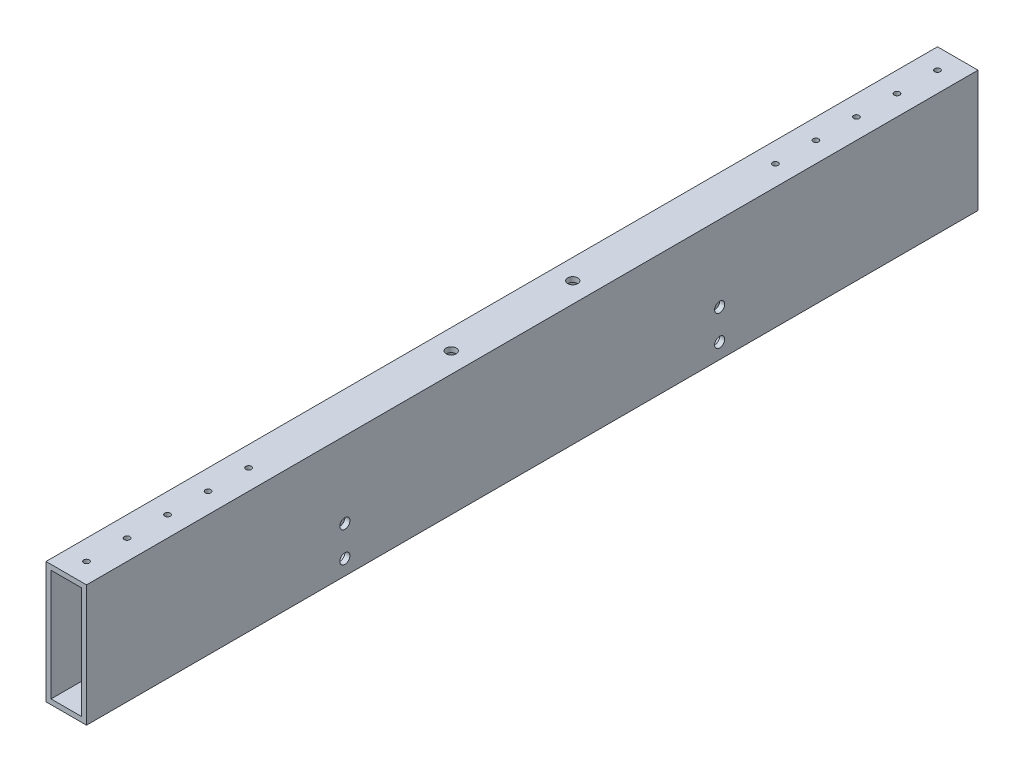
SolidWorks part; units mm, degrees
material "6061-T6 (SS)"
ref_plane "Front Plane" through (0, 0, 0) normal (0, 0, 1) x (1, 0, 0)
ref_plane "Top Plane" through (0, 0, 0) normal (0, 1, 0) x (1, 0, 0)
ref_plane "Right Plane" through (0, 0, 0) normal (1, 0, 0) x (0, 0, -1)
sketch "Sketch1" plane through (0, 0, 0) normal (0, 0, 1) x (1, 0, 0)
  line L0 (9.525, 34.925) -> (-9.525, 34.925)
  line L1 (12.7, 38.1) -> (-12.7, 38.1)
  line L2 (12.7, 38.1) -> (12.7, -38.1)
  line L3 (12.7, -38.1) -> (-12.7, -38.1)
  line L4 (-12.7, 38.1) -> (-12.7, -38.1)
  line L5 (12.7, 38.1) -> (-12.7, -38.1) construction
  line L6 (12.7, -38.1) -> (-12.7, 38.1) construction
  line L7 (-9.525, 34.925) -> (-9.525, -34.925)
  line L8 (9.525, -34.925) -> (-9.525, -34.925)
  line L9 (9.525, 34.925) -> (9.525, -34.925)
  point P0 (0, 0)
  dimension "D1" = 76.2
  dimension "D2" = 25.4
  dimension "D3" = 3.175
extrude "Boss-Extrude1" add sketch "Sketch1" along normal mid plane 558.8
sketch "Sketch2" plane through (0, 38.1, 0) normal (0, 1, 0) x (1, 0, 0)
  line L1 (12.7, 279.4) -> (-12.7, 279.4) construction
  circle A0 centre (0, 266.7) radius 1.7272
  circle A1 centre (0, 241.3) radius 1.7272
  circle A2 centre (0, 215.9) radius 1.7272
  circle A3 centre (0, 190.5) radius 1.7272
  circle A8 centre (0, 165.1) radius 1.7272
  dimension "D1" = 3.4544
  dimension "D2" = 12.7
  dimension "D3" = 5
sketch "Sketch3" plane through (0, -38.1, 0) normal (0, -1, 0) x (1, 0, 0)
  line L2 (9.525, 279.4) -> (-9.525, 279.4) construction
  circle A0 centre (0, 254) radius 1.7272
  circle A1 centre (0, 203.2) radius 1.7272
  circle A2 centre (0, 152.4) radius 1.7272
  circle A3 centre (0, 101.6) radius 1.7272
  circle A4 centre (0, 50.8) radius 1.7272
  circle A5 centre (0, 0) radius 1.7272
  circle A6 centre (0, -50.8) radius 1.7272
  circle A7 centre (0, -101.6) radius 1.7272
  circle A8 centre (0, -152.4) radius 1.7272
  circle A9 centre (0, -203.2) radius 1.7272
  circle A10 centre (0, -254) radius 1.7272
  point P6 (0, 279.4)
  dimension "D1" = 3.4544
  dimension "D2" = 25.4
  dimension "D4" = 50.8
  dimension "D3" = 11
extrude "Cut-Extrude2" cut sketch "Sketch3" against normal blind 6.35
hole_wizard "1/4 (0.25) Diameter Hole1" positions "Sketch9" profile "Sketch8" hole size "1/4" standard "ANSI Inch"
sketch "Sketch9" plane through (-12.7, 0, 0) normal (-1, 0, 0) x (0, 0, 1)
  line L0 (-117.475, -28.575) -> (117.475, -28.575) construction
  line L2 (279.4, -38.1) -> (-279.4, -38.1) construction
  line L4 (-127, 0) -> (127, 0) construction
  point P10 (-117.475, -28.575)
  point P11 (117.475, -28.575)
  point P25 (-117.475, -9.525)
  point P27 (117.475, -9.525)
  point P34 (0, -28.575)
  dimension "D1" = 234.95
  dimension "D2" = 9.525
  dimension "D3" = 254
  dimension "D4" = 19.05
  dimension "D5" = 19.05
sketch "Sketch8" plane through (-12.7, -28.575, -117.475) normal (0, 1, 0) x (0, 0, 1)
  line L0 (0, 0) -> (0, 27.3077)
  line L1 (0, 27.3077) -> (3.175, 25.4)
  line L2 (3.175, 25.4) -> (3.175, 0)
  line L5 (3.175, 0) -> (0, 0)
  line L10 (0, 27.3077) -> (-3.175, 25.4) construction
  line L11 (0, -6.35) -> (0, 107.95) construction
  dimension "Hole Dia." = 6.35
  dimension "Hole Depth" = 25.4
  dimension "Drill Angle" = 118
hole_wizard "1/4 (0.25) Diameter Hole2" positions "Sketch12" profile "Sketch13" hole size "1/4" standard "ANSI Inch" end condition through all
sketch "Sketch12" plane through (0, 38.1, 0) normal (0, 1, 0) x (1, 0, 0)
  line L0 (12.7, -279.4) -> (-12.7, -279.4) construction
  line L1 (0, 38.1) -> (0, -38.1) construction
  point P20 (0, -38.1)
  point P22 (0, 38.1)
  point P27 (0, -279.4)
  point P32 (0, 0)
  dimension "D7" = 76.2
sketch "Sketch13" plane through (0, 38.1, 38.1) normal (1, 0, 0) x (0, 0, 1)
  line L0 (0, 0) -> (0, 76.2)
  line L1 (0, 76.2) -> (3.175, 76.2)
  line L2 (3.175, 76.2) -> (3.175, 0)
  line L5 (3.175, 0) -> (0, 0)
  line L11 (0, -6.35) -> (0, 107.95) construction
  dimension "Thru Hole Dia." = 6.35
  dimension "Thru Hole Depth" = 76.2
extrude "Cut-Extrude4" cut sketch "Sketch2" against normal blind 6.35
mirror "Mirror1" about plane through (0, 0, 0) normal (0, 0, 1) of "Cut-Extrude4"
